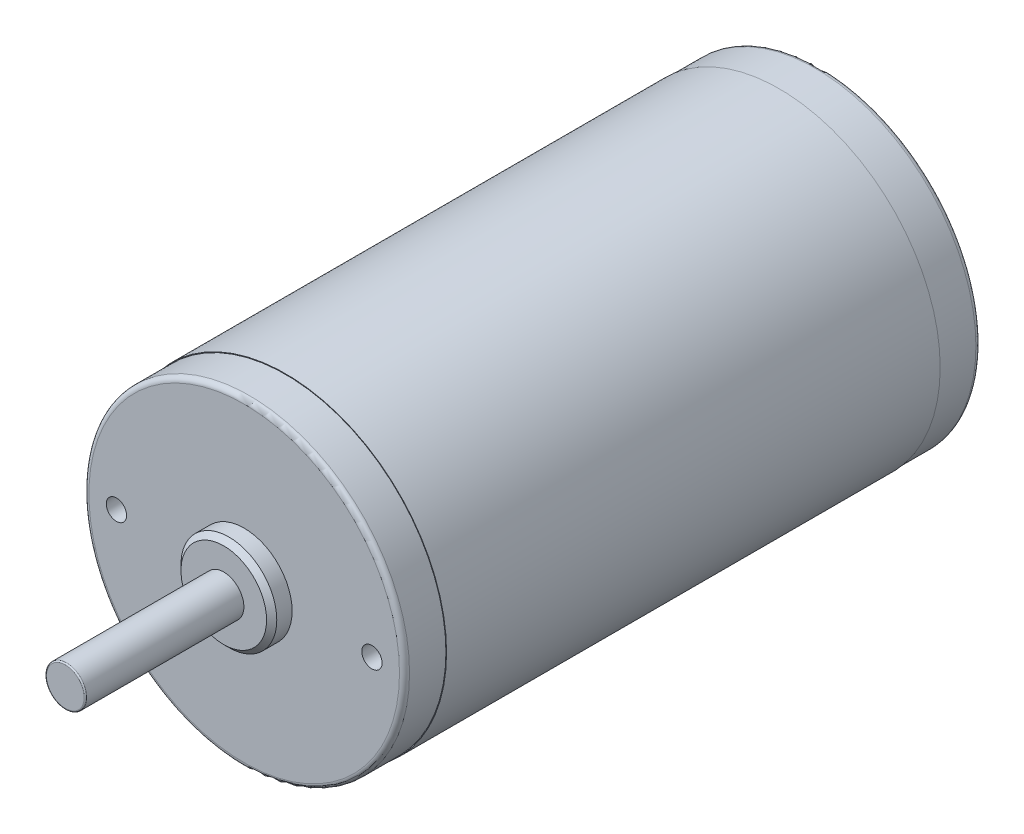
SolidWorks part; units mm, degrees
ref_plane "Front Plane" through (0, 0, 0) normal (0, 0, 1) x (1, 0, 0)
ref_plane "Top Plane" through (0, 0, 0) normal (0, 1, 0) x (1, 0, 0)
ref_plane "Right Plane" through (0, 0, 0) normal (1, 0, 0) x (0, 0, -1)
ref_plane "Plane1" through (0, 109.2962, 0) normal (0, -1, 0) x (1, 0, 0)
sketch "Sketch1" plane through (0, 109.2962, 0) normal (0, -1, 0) x (1, 0, 0)
  line L0 (67.564, 10.8204) -> (35.56, 10.8204)
  line L1 (35.56, 10.8204) -> (35.56, -87.3252)
  line L2 (35.56, -87.3252) -> (67.564, -87.3252)
  line L3 (67.564, -87.3252) -> (67.564, 10.8204)
  line L4 (35.56, 10.8204) -> (35.56, -87.3252) construction
revolve "Revolve1" add sketch "Sketch1" angle 360 about L4 other way angle 360 reverse direction yes
sketch "Sketch2" plane through (0, 0, 10.8204) normal (0, 0, 1) x (1, 0, 0)
  circle A0 centre (35.56, 109.2962) radius 31.877
extrude "Boss-Extrude1" add sketch "Sketch2" along normal blind 8.2296
ref_plane "Plane2" through (0, 0, 18.542) normal (0, 0, -1) x (-1, 0, 0)
sketch "Sketch5" plane through (0, 0, 18.542) normal (0, 0, -1) x (-1, 0, 0)
  circle A0 centre (-35.56, 109.2962) radius 9.525
extrude "Boss-Extrude2" add sketch "Sketch5" against normal blind 4.572
sketch "Sketch6" plane through (0, 0, 23.114) normal (0, 0, 1) x (1, 0, 0)
  circle A0 centre (35.56, 109.2962) radius 4
extrude "Boss-Extrude3" add sketch "Sketch6" along normal blind 31.5
sketch "Sketch8" plane through (0, 0, -87.3252) normal (0, 0, -1) x (-1, 0, 0)
  circle A0 centre (-35.56, 109.2962) radius 31.877
extrude "Boss-Extrude4" add sketch "Sketch8" along normal blind 8.2296
sketch "Sketch9" plane through (0, 0, -95.5548) normal (0, 0, -1) x (-1, 0, 0)
  circle A0 centre (-35.56, 109.2962) radius 15.0368
extrude "Boss-Extrude5" add sketch "Sketch9" along normal blind 4.7625
ref_plane "Plane3" [suppressed] through (0, 120.5036, 0) normal (0, 1, 0) x (-1, 0, 0)
ref_plane "Plane4" [suppressed] through (0, 127.9033, 0) normal (0, 1, 0) x (-1, 0, 0)
hole_wizard "Hole2" positions "Sketch13" profile "Sketch12" legacy
sketch "Sketch13" plane through (0, 0, 19.05) normal (0, 0, 1) x (1, 0, 0)
  point P0 (60.96, 109.2962)
sketch "Sketch12" plane through (60.96, 109.2962, 19.05) normal (1, 0, 0) x (0, -1, 0)
  line L0 (0, 0) -> (0, 14.8277)
  line L1 (0, 14.8277) -> (2.0193, 13.6144)
  line L2 (2.0193, 13.6144) -> (2.0193, 0)
  line L4 (2.0193, 0) -> (0, 0)
  line L6 (0, 14.8277) -> (-2.0193, 13.6144) construction
  line L7 (0, -4.2442) -> (0, 117.3081) construction
  dimension "Diameter" = 4.0386
  dimension "Depth" = 13.6144
  dimension "Drill Angle" = 118
hole_wizard "Hole3" positions "Sketch15" profile "Sketch14" legacy
sketch "Sketch15" plane through (0, 0, 19.05) normal (0, 0, 1) x (1, 0, 0)
  point P0 (10.16, 109.2962)
sketch "Sketch14" plane through (10.16, 109.2962, 19.05) normal (1, 0, 0) x (0, -1, 0)
  line L0 (0, 0) -> (0, 14.8277)
  line L1 (0, 14.8277) -> (2.0193, 13.6144)
  line L2 (2.0193, 13.6144) -> (2.0193, 0)
  line L4 (2.0193, 0) -> (0, 0)
  line L6 (0, 14.8277) -> (-2.0193, 13.6144) construction
  line L7 (0, -4.2442) -> (0, 117.3081) construction
  dimension "Diameter" = 4.0386
  dimension "Depth" = 13.6144
  dimension "Drill Angle" = 118
chamfer "Chamfer1" distance 1.016 angle 45 1 edges at (45.085, 109.2962, 23.114) first distance on face at (45.085, 109.2962, 23.114)
fillet "Fillet1" radius 0.254 1 edges at (39.56, 109.2962, 54.614) tangent propagation no
fillet "Fillet2" radius 1 1 edges at (3.683, 109.2962, -95.5548) tangent propagation no
fillet "Fillet3" radius 1 1 edges at (67.437, 109.2962, 19.05) tangent propagation no
fillet "Fillet4" radius 1 1 edges at (20.5232, 109.2962, -100.3173) tangent propagation no
ref_plane "Plane5" [suppressed] through (39.56, 0, 0) normal (1, 0, 0) x (0, 0, -1)
